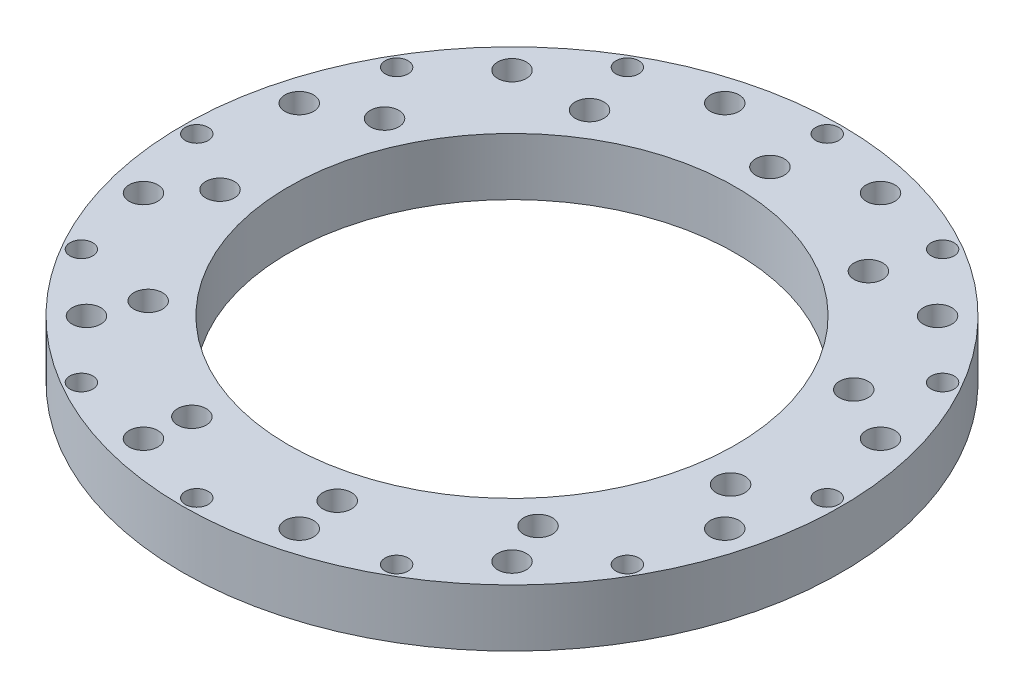
SolidWorks part; units mm, degrees
ref_plane "Front Plane" through (0, 0, 0) normal (0, 0, 1) x (1, 0, 0)
ref_plane "Top Plane" through (0, 0, 0) normal (0, 1, 0) x (1, 0, 0)
ref_plane "Right Plane" through (0, 0, 0) normal (1, 0, 0) x (0, 0, -1)
sketch "Sketch1" plane through (0, 0, 0) normal (0, 1, 0) x (1, 0, 0)
  line L0 (0, 0) -> (0, 52.5) construction
  line L1 (0, 0) -> (13.588, 50.7111) construction
  circle A12 centre (0, 0) radius 39
  circle A13 centre (0, 0) radius 57.5
  circle A14 centre (0, 0) radius 55 construction
  circle A15 centre (0, 55) radius 2
  circle A16 centre (27.5, 47.6314) radius 2
  circle A17 centre (47.6314, 27.5) radius 2
  circle A18 centre (55, 0) radius 2
  circle A19 centre (47.6314, -27.5) radius 2
  circle A20 centre (27.5, -47.6314) radius 2
  circle A21 centre (0, -55) radius 2
  circle A22 centre (-27.5, -47.6314) radius 2
  circle A23 centre (-47.6314, -27.5) radius 2
  circle A24 centre (-55, 0) radius 2
  circle A25 centre (-47.6314, 27.5) radius 2
  circle A26 centre (-27.5, 47.6314) radius 2
  circle A27 centre (0, 0) radius 52.5 construction
  circle A34 centre (13.588, 50.7111) radius 2.5
  circle A35 centre (37.1231, 37.1231) radius 2.5
  circle A36 centre (50.7111, 13.588) radius 2.5
  circle A37 centre (50.7111, -13.588) radius 2.5
  circle A38 centre (37.1231, -37.1231) radius 2.5
  circle A39 centre (13.588, -50.7111) radius 2.5
  circle A40 centre (-13.588, -50.7111) radius 2.5
  circle A41 centre (-37.1231, -37.1231) radius 2.5
  circle A42 centre (-50.7111, -13.588) radius 2.5
  circle A43 centre (-50.7111, 13.588) radius 2.5
  circle A44 centre (-37.1231, 37.1231) radius 2.5
  circle A45 centre (-13.588, 50.7111) radius 2.5
  point P21 (0, 0)
  point P28 (0, 0)
  point P56 (0, 0)
  point P60 (0, 0)
  dimension "D1" = 105
  dimension "D2" = 15
  dimension "D4" = 115
  dimension "D5" = 78
  dimension "D6" = 110
  dimension "D7" = 4
  dimension "D3" = 5
  dimension "D8" = 12
extrude "Boss-Extrude1" add sketch "Sketch1" along normal blind 10
sketch "Sketch2" plane through (0, 10, 0) normal (0, 1, 0) x (1, 0, 0)
  circle A0 centre (0, 0) radius 45 construction
  circle A1 centre (0, 45) radius 2.5
  circle A2 centre (24.3288, 37.8564) radius 2.5
  circle A3 centre (40.9334, 18.6937) radius 2.5
  circle A4 centre (44.542, -6.4042) radius 2.5
  circle A5 centre (34.0087, -29.4687) radius 2.5
  circle A6 centre (12.678, -43.1772) radius 2.5
  circle A7 centre (-12.678, -43.1772) radius 2.5
  circle A8 centre (-34.0087, -29.4687) radius 2.5
  circle A9 centre (-44.542, -6.4042) radius 2.5
  circle A10 centre (-40.9334, 18.6937) radius 2.5
  circle A11 centre (-24.3288, 37.8564) radius 2.5
  point P27 (0, 0)
  dimension "D1" = 90
  dimension "D2" = 5
extrude "Cut-Extrude1" cut sketch "Sketch2" against normal blind 10
